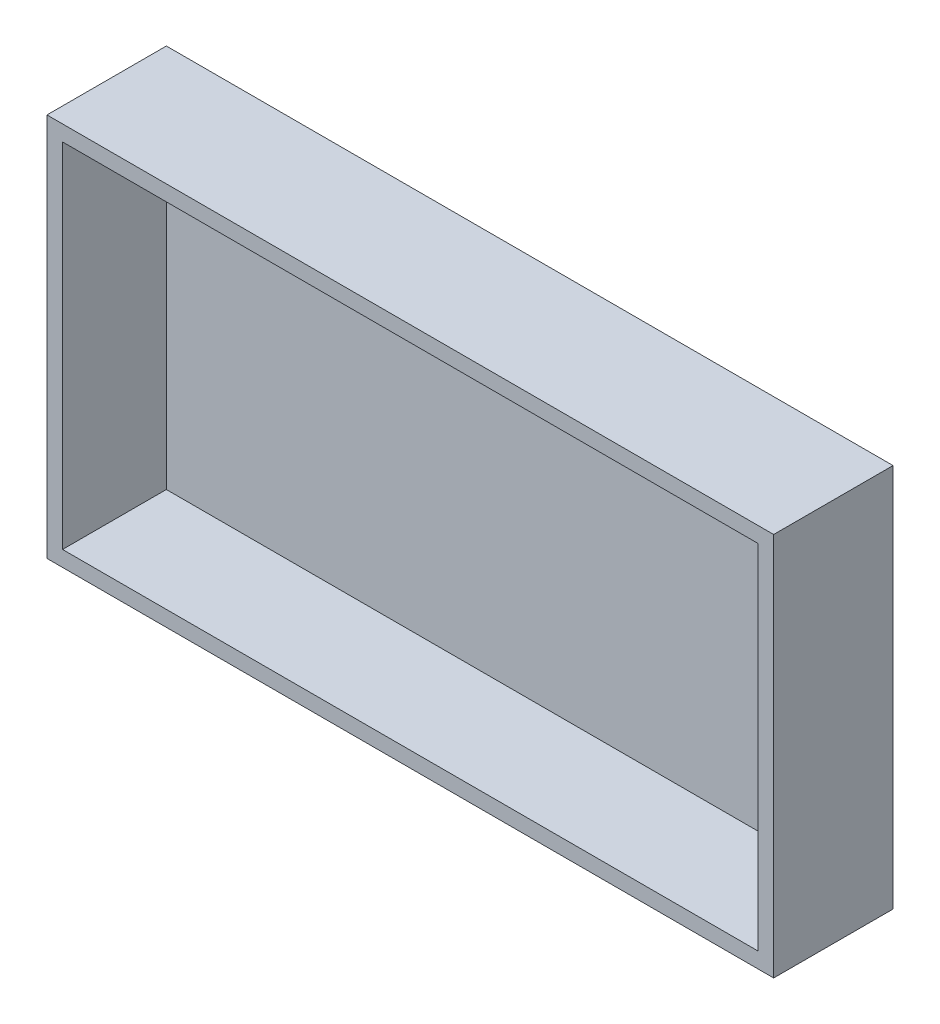
SolidWorks part; units mm, degrees
ref_plane "前视基准面" through (0, 0, 0) normal (0, 0, 1) x (1, 0, 0)
ref_plane "上视基准面" through (0, 0, 0) normal (0, 1, 0) x (1, 0, 0)
ref_plane "右视基准面" through (0, 0, 0) normal (1, 0, 0) x (0, 0, -1)
sketch "草图1" plane through (0, 0, 0) normal (0, 0, 1) x (1, 0, 0)
  line L1 (-35, 18.5) -> (35, 18.5)
  line L2 (-35, 18.5) -> (-35, -18.5)
  line L3 (-35, -18.5) -> (35, -18.5)
  line L4 (35, 18.5) -> (35, -18.5)
  line L5 (-35, 18.5) -> (35, -18.5) construction
  line L6 (-35, -18.5) -> (35, 18.5) construction
  point P0 (0, 0)
  dimension "D1" = 37
  dimension "D2" = 70
extrude "凸台-拉伸1" add sketch "草图1" along normal blind 11.5
shell "抽壳1" thickness 1.5 removed face at (0, 0, 11.5)
